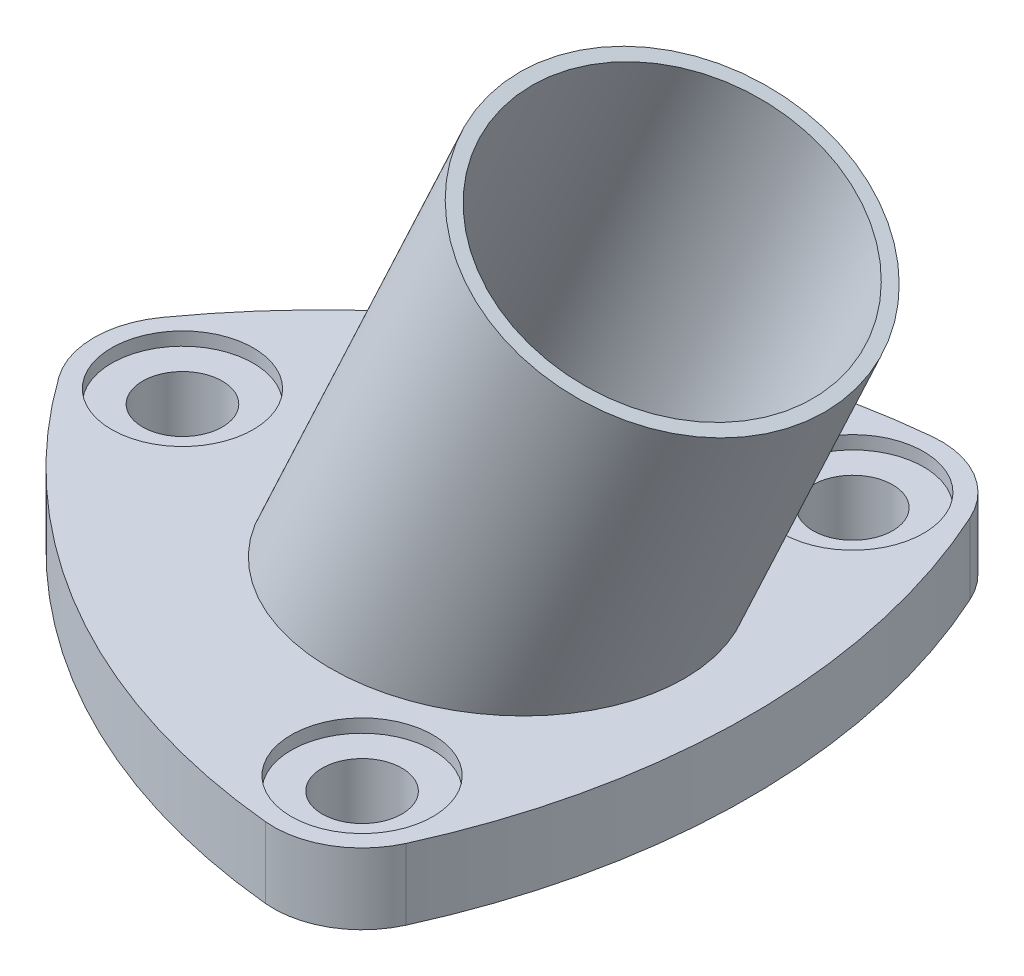
SolidWorks part; units mm, degrees
ref_plane "前基準面" through (0, 0, 0) normal (0, 0, 1) x (1, 0, 0)
ref_plane "上基準面" through (0, 0, 0) normal (0, 1, 0) x (1, 0, 0)
ref_plane "右基準面" through (0, 0, 0) normal (1, 0, 0) x (0, 0, -1)
sketch "草圖1" plane through (0, 0, 0) normal (0, 1, 0) x (1, 0, 0)
  line L0 (0, 0) -> (-32, 0) construction
  circle A0 centre (0, 0) radius 32 construction
  circle A1 centre (-32, 0) radius 4.5
  circle A2 centre (16, 27.7128) radius 4.5
  circle A3 centre (16, -27.7128) radius 4.5
  arc A4 (-40.1343, -5.8166) -> (-40.1343, 5.8166) centre (-32, 0) cw
  arc A5 (15.0299, -37.6656) -> (25.1045, -31.8491) centre (16, -27.7128) ccw
  arc A6 (15.0299, 37.6656) -> (25.1045, 31.8491) centre (16, 27.7128) cw
  arc A8 (-40.1343, 5.8166) -> (15.0299, 37.6656) centre (22.5, -38.9711) cw
  arc A10 (-40.1343, -5.8166) -> (15.0299, -37.6656) centre (22.5, 38.9711) ccw
  arc A12 (25.1045, 31.8491) -> (25.1045, -31.8491) centre (-45, 0) cw
  dimension "D1" = 32
  dimension "D4" = 9
  dimension "D2" = 10
  dimension "D3" = 10
  dimension "D6" = 10
  dimension "D5" = 3
extrude "填料-伸長1" add sketch "草圖1" along normal blind 8
sketch "草圖3" plane through (0, 0, 0) normal (0, 0, 1) x (1, 0, 0)
  line L0 (0, 0) -> (36.7946, 0) construction
  line L1 (36.7946, 0) -> (0, 0) construction
  line L2 (0, 0) -> (23.3154, 50) construction
  dimension "D1" = 65
  dimension "D2" = 50
ref_plane "平面2" through (23.3154, 50, 0) normal (0.4226, 0.9063, 0) x (0.9063, -0.4226, 0)
sketch "草圖4" plane through (23.3154, 50, 0) normal (0.4226, 0.9063, 0) x (0.9063, -0.4226, 0)
  circle A0 centre (0, 0) radius 17.5
  circle A1 centre (0, 0) radius 19
  dimension "D1" = 38
  dimension "D2" = 35
sketch "草圖5" plane through (0, 8, 0) normal (0, 1, 0) x (1, 0, 0)
  circle A0 centre (-32, 0) radius 8
  circle A1 centre (16, 27.7128) radius 8
  circle A2 centre (16, -27.7128) radius 8
  circle A3 centre (16, 27.7128) radius 4.5 construction
  dimension "D1" = 16
  dimension "D2" = 3
extrude "除料-伸長2" cut sketch "草圖5" against normal blind 1.5
extrude "填料-伸長3" add sketch "草圖4" against normal up to surface (55.2017 mm away) contours A1 up to face at (-32, 8, 8)
extrude "除料-伸長3" cut sketch "草圖4<3>" against normal through all contours A0
sketch "草圖4<3>" plane through (23.3154, 50, 0) normal (0.4226, 0.9063, 0) x (0.9063, -0.4226, 0) same geometry as "草圖4"
